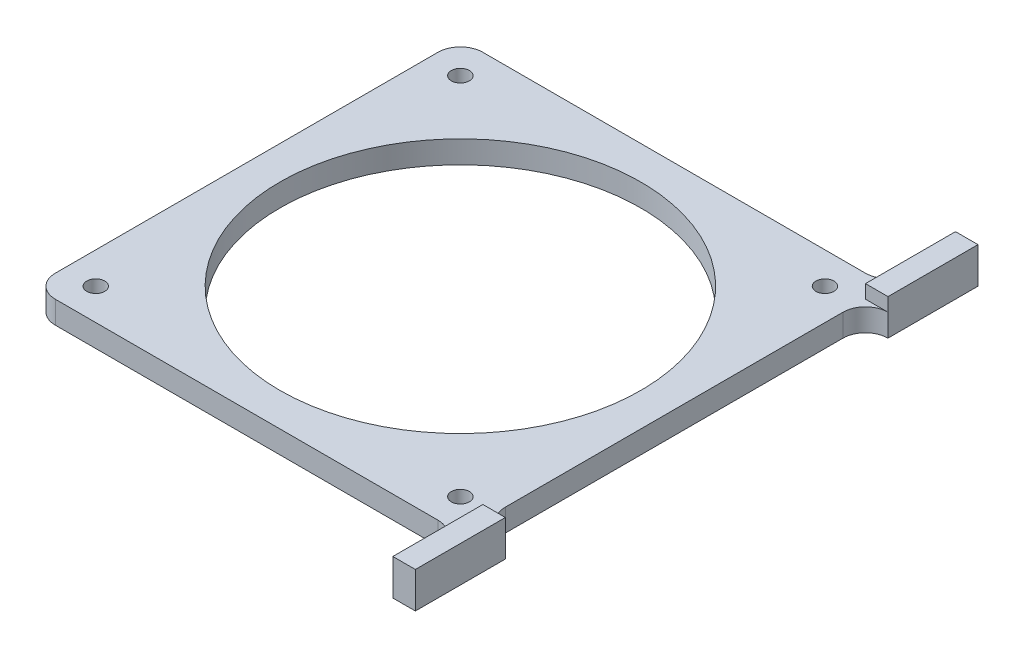
SolidWorks part; units mm, degrees
ref_plane "Front Plane" through (0, 0, 0) normal (0, 0, 1) x (1, 0, 0)
ref_plane "Top Plane" through (0, 0, 0) normal (0, 1, 0) x (1, 0, 0)
ref_plane "Right Plane" through (0, 0, 0) normal (1, 0, 0) x (0, 0, -1)
sketch "Sketch1" plane through (0, 0, 0) normal (0, 1, 0) x (1, 0, 0)
  line L1 (-47.5, -47.5) -> (47.5, -47.5)
  line L2 (-47.5, -47.5) -> (-47.5, 47.5)
  line L3 (-47.5, 47.5) -> (47.5, 47.5)
  line L4 (47.5, -47.5) -> (47.5, 47.5)
  line L5 (-47.5, -47.5) -> (47.5, 47.5) construction
  line L6 (-47.5, 47.5) -> (47.5, -47.5) construction
  line L7 (-40.5, -40.5) -> (40.5, -40.5)
  line L8 (-40.5, -40.5) -> (-40.5, 40.5)
  line L9 (-40.5, 40.5) -> (40.5, 40.5)
  line L10 (40.5, -40.5) -> (40.5, 40.5)
  line L11 (-40.5, -40.5) -> (40.5, 40.5) construction
  line L12 (-40.5, 40.5) -> (40.5, -40.5) construction
  circle A0 centre (0, 0) radius 40.1
  point P0 (0, 0)
  dimension "D3" = 80.2
  dimension "D1" = 95
  dimension "D2" = 95
  dimension "D4" = 81
extrude "Boss-Extrude1" add sketch "Sketch1" along normal blind 5 contours L7 L10 L9 L8 A0 | L1 L4 L3 L2 L10 L7 L8 L9 region at (-46.1565, 0, 0) region at (-40.3854, 0, 0)
hole_wizard "Ø4.0mm Dowel Hole1" positions "Sketch2" profile "Sketch4" hole size "Ø4.0" standard "ANSI Metric" end condition through all
sketch "Sketch2" plane through (0, 0, 0) normal (0, -1, 0) x (-1, 0, 0)
  point P0 (40.5, -40.5)
  point P3 (-40.5, -40.5)
  point P6 (-40.5, 40.5)
  point P9 (40.5, 40.5)
sketch "Sketch4" plane through (-40.5, 0, 40.5) normal (1, 0, 0) x (0, 0, -1)
  line L0 (0, 0) -> (0, 5)
  line L1 (0, 5) -> (2, 5)
  line L2 (2, 5) -> (2, 0)
  line L5 (2, 0) -> (0, 0)
  line L11 (0, -6.35) -> (0, 107.95) construction
  dimension "Thru Hole Dia." = 4
  dimension "Thru Hole Depth" = 5
sketch "Sketch5" plane through (0, 0, 0) normal (0, 1, 0) x (1, 0, 0)
  line L0 (47.5, -47.5) -> (47.5, 47.5) construction
  line L1 (47.5, -42.5) -> (52.5, -42.5)
  line L2 (47.5, -42.5) -> (47.5, -62.5)
  line L3 (47.5, -62.5) -> (52.5, -62.5)
  line L4 (52.5, -42.5) -> (52.5, -62.5)
  line L6 (47.5, 42.5) -> (52.5, 42.5)
  line L7 (47.5, 42.5) -> (47.5, 62.5)
  line L8 (47.5, 62.5) -> (52.5, 62.5)
  line L9 (52.5, 42.5) -> (52.5, 62.5)
  dimension "D1" = 15
  dimension "D2" = 15
  dimension "D3" = 5
  dimension "D4" = 5
  dimension "D5" = 5
  dimension "D6" = 5
extrude "Boss-Extrude2" add sketch "Sketch5" along normal blind 5
sketch "Sketch6" plane through (0, 5, 0) normal (0, 1, 0) x (1, 0, 0)
  line L1 (47.5, -62.5) -> (52.5, -62.5)
  line L2 (47.5, -62.5) -> (47.5, -42.5)
  line L3 (47.5, -42.5) -> (52.5, -42.5)
  line L4 (52.5, -62.5) -> (52.5, -42.5)
  line L5 (47.5, 42.5) -> (52.5, 42.5)
  line L6 (47.5, 42.5) -> (47.5, 62.5)
  line L7 (47.5, 62.5) -> (52.5, 62.5)
  line L8 (52.5, 42.5) -> (52.5, 62.5)
extrude "Boss-Extrude3" add sketch "Sketch6" along normal blind 3
fillet "Fillet1" radius 5 6 edges at (-47.5, 2.5, -47.5) (-47.5, 2.5, 47.5) (47.5, 2.5, 47.5) (47.5, 2.5, 42.5) (47.5, 2.5, -42.5) (47.5, 2.5, -47.5)
